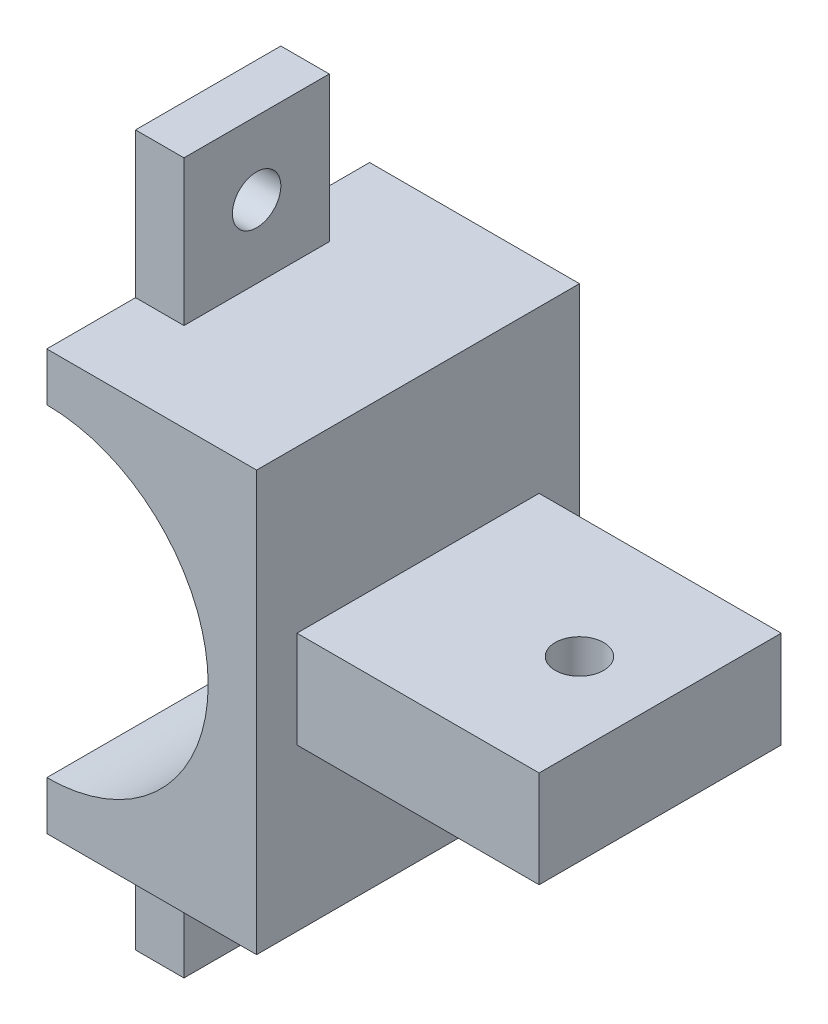
SolidWorks part; units mm, degrees
ref_plane "Спереди" through (0, 0, 0) normal (0, 0, 1) x (1, 0, 0)
ref_plane "Сверху" through (0, 0, 0) normal (0, 1, 0) x (1, 0, 0)
ref_plane "Справа" through (0, 0, 0) normal (1, 0, 0) x (0, 0, -1)
sketch "Эскиз1" plane through (0, 0, 0) normal (0, 0, 1) x (1, 0, 0)
  line L0 (0, 10) -> (0, 13)
  line L1 (0, -10) -> (0, -13)
  line L2 (0, 0) -> (10, 0) construction
  line L3 (0, 0) -> (0, -10) construction
  line L4 (0, 13) -> (13, 13)
  line L5 (10, 0) -> (55, 0) construction
  line L6 (13, 13) -> (13, -13)
  line L7 (13, -13) -> (0, -13)
  arc A0 (0, 10) -> (0, -10) centre (0, 0) cw
  dimension "D1" = 10
  dimension "D4" = 13
  dimension "D2" = 3
  dimension "D3" = 20
  dimension "D5" = 3
extrude "Бобышка-Вытянуть1" add sketch "Эскиз1" along normal blind 20
sketch "Эскиз7" plane through (0, 0, 0) normal (-1, 0, 0) x (0, 0, 1)
  line L1 (20, 10) -> (0, 10) construction
  line L2 (5.5, 10) -> (5.5, 22)
  line L3 (5.5, 22) -> (14.5, 22)
  line L4 (14.5, 22) -> (14.5, 10)
  line L6 (5.5, 10) -> (14.5, 10)
  line L7 (10, 10) -> (10, 17.5) construction
  line L8 (10, -10) -> (10, -17.5) construction
  line L10 (20, -10) -> (0, -10) construction
  line L11 (14.5, -10) -> (5.5, -10)
  line L12 (5.5, -10) -> (5.5, -22)
  line L13 (5.5, -22) -> (14.5, -22)
  line L14 (14.5, -22) -> (14.5, -10)
  circle A0 centre (10, 17.5) radius 1.5
  circle A1 centre (10, -17.5) radius 1.5
  dimension "D1" = 3
  dimension "D2" = 12
  dimension "D3" = 7.5
  dimension "D4" = 9
  dimension "D5" = 10
extrude "Бобышка-Вытянуть3" add sketch "Эскиз7" against normal blind 3
sketch "Эскиз8" plane through (13, 0, 0) normal (1, 0, 0) x (0, 0, -1)
  line L0 (0, 0) -> (-20, 0) construction
  line L1 (-20, -13) -> (-20, 13) construction
  line L2 (-10, 0) -> (-10, 3) construction
  line L3 (-10, 0) -> (-10, -3) construction
  line L5 (-17.5, 3) -> (-17.5, -3)
  line L6 (-17.5, -3) -> (-2.5, -3)
  line L7 (-2.5, -3) -> (-2.5, 3)
  line L10 (-17.5, 3) -> (-10, 3)
  line L11 (-10, 3) -> (-2.5, 3)
  dimension "D1" = 15
  dimension "D2" = 6
  dimension "D3" = 3
extrude "Бобышка-Вытянуть4" add sketch "Эскиз8" along normal blind 15
sketch "Эскиз9" plane through (0, 3, 0) normal (0, 1, 0) x (1, 0, 0)
  line L0 (28, -10) -> (23, -10) construction
  line L1 (28, -2.5) -> (28, -17.5) construction
  circle A0 centre (23, -10) radius 1.5
  dimension "D1" = 3
  dimension "D2" = 5
extrude "Вырез-Вытянуть1" cut sketch "Эскиз9" against normal blind 15
sketch "Эскиз6" plane through (0, 0, 0) normal (-1, 0, 0) x (0, 0, 1)
  line L0 (10, 10) -> (10, -10) construction
  line L1 (20, 10) -> (0, 10) construction
  line L2 (20, -10) -> (0, -10) construction
  line L3 (10, 10) -> (5.5, 10)
  line L4 (5.5, 10) -> (5.5, 22)
  line L5 (5.5, 22) -> (14.5, 22)
  line L6 (14.5, 22) -> (14.5, 10)
  line L7 (14.5, 10) -> (10, 10)
  line L8 (10, -10) -> (5.5, -10)
  line L9 (5.5, -10) -> (5.5, -22)
  line L10 (5.5, -22) -> (14.5, -22)
  line L11 (14.5, -22) -> (14.5, -10)
  line L12 (14.5, -10) -> (10, -10)
  circle A0 centre (10, 17.5) radius 1.5
  circle A1 centre (10, -17.5) radius 1.5
  dimension "D1" = 3
  dimension "D6" = 4.5
  dimension "D2" = 4.5
  dimension "D3" = 7.5
  dimension "D4" = 12
  dimension "D5" = 4.5
  dimension "D7" = 7.5
extrude "Бобышка-Вытянуть2" add sketch "Эскиз6" against normal blind 3
